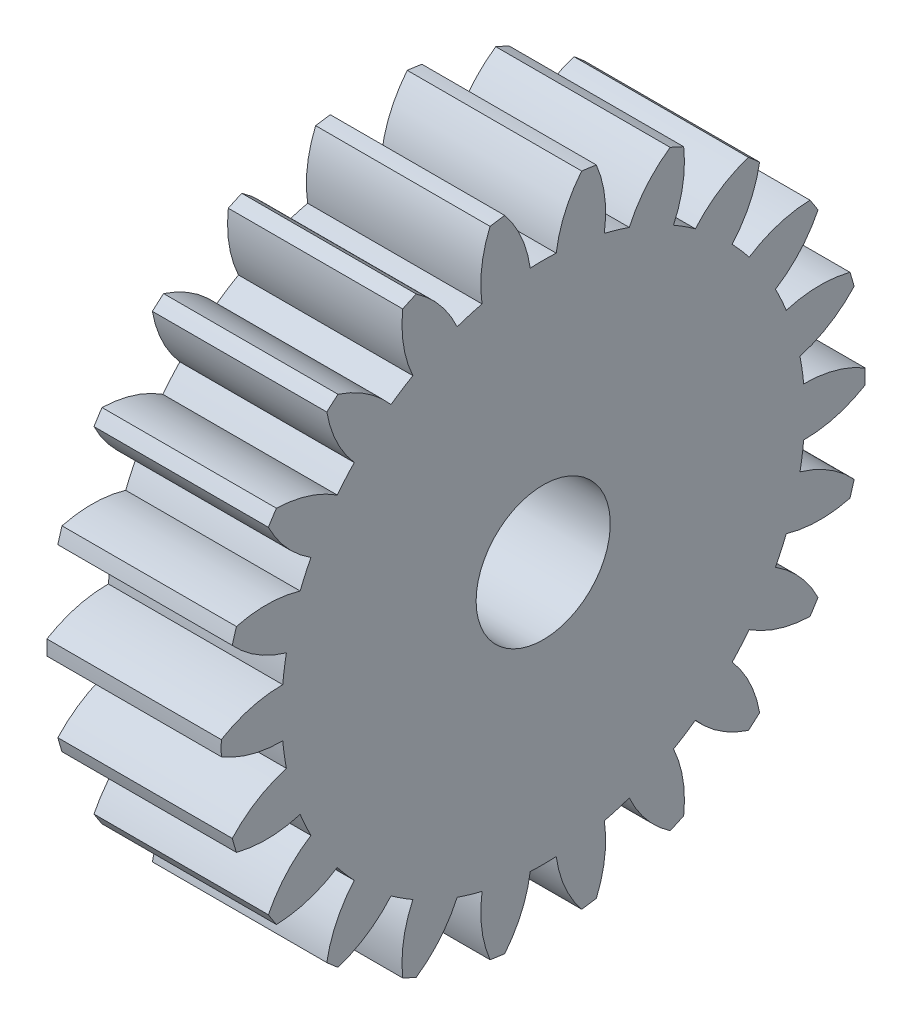
SolidWorks part; units mm, degrees
ref_plane "Plane1" through (0, 0, 0) normal (0, 0, 1) x (1, 0, 0)
ref_plane "Plane2" through (0, 0, 0) normal (0, 1, 0) x (1, 0, 0)
ref_plane "Plane3" through (0, 0, 0) normal (1, 0, 0) x (0, 0, -1)
other "Configuration Table"
sketch "HoldingSke" plane through (0, 0, 0) normal (0, 1, 0) x (1, 0, 0)
  line L0 (0, 0) -> (0.4636, -0.1873)
  line L1 (-15, 0) -> (100, 0) construction
  line L2 (0, 0) -> (-2.1039, 2.3779)
  line L3 (0, 0) -> (-11.863, 4.5341)
  line L4 (0, 0) -> (8.0072, 3.2351)
  line L5 (0, 0) -> (-15.9282, -5.9407)
  line L6 (0, 0) -> (-10.7765, -7.2709)
  line L7 (-2.1039, 2.3779) -> (1.5554, 18.9794)
  line L8 (-76.2, 54.61) -> (-74.4, 54.61)
  line L9 (-71.009, 38.7566) -> (-53.1078, 45.2721)
  line L10 (-76.2, 71.12) -> (104.1128, 71.12)
  line L11 (0, 0) -> (-13, 0)
  line L12 (-76.2, 101.6) -> (-76.133, 101.6)
  line L13 (24.9733, 27.94) -> (52.9518, 28.4284)
  line L14 (24.9733, 27.94) -> (24.9743, 27.94)
  line L15 (24.9733, 27.94) -> (100.4006, 29.5858)
  line L16 (-63.627, -2) -> (-12.827, -2)
  circle A0 centre (0, 0) radius 5
  circle A1 centre (0, 0) radius 6
  circle A2 centre (0, 0) radius 6
  circle A3 centre (0, 0) radius 5
  dimension "Num_teeth" = 22
  dimension "Pitch_radius" = 180.3128
  dimension "Width" = 13
  dimension "Thickness" = 13
sketch "BasProSke" plane through (0, 0, 0) normal (0, 1, 0) x (1, 0, 0)
  line L0 (-10, 0) -> (60, 0) construction
  line L1 (0, 0) -> (0, 24)
  line L2 (0, 0) -> (13, 0)
  line L3 (13, 0) -> (13, 24)
  line L4 (13, 24) -> (0, 24)
  dimension "Thickness" = 13
  dimension "Diameter" = 48
revolve "Base-Revolve" add sketch "BasProSke" angle 360 about L0
sketch "TooCutSke" plane through (0, 0, 0) normal (1, 0, 0) x (0, 0, -1)
  line L1 (0, 0) -> (0, 107) construction
  line L2 (0, 0) -> (-1.6867, 21.9352) construction
  line L3 (0, 0) -> (-6.2482, 43.4572) construction
  line L4 (-1.6867, 21.9352) -> (-3.1241, 21.7286) construction
  arc A0 (0.9682, 19.4749) -> (-0.9682, 19.4749) centre (0, 0) ccw
  arc A1 (2.8856, 23.8515) -> (-2.8856, 23.8515) centre (0, 0) ccw
  circle A2 centre (0, 0) radius 22 construction
  circle A3 centre (0, 0) radius 20.6732 construction
  arc A4 (-0.9682, 19.4749) -> (-2.8856, 23.8515) centre (-9.6845, 18.2645) ccw
  arc A5 (2.8856, 23.8515) -> (0.9682, 19.4749) centre (9.6845, 18.2645) ccw
extrude "ToothCut" cut sketch "TooCutSke" along normal through all
fillet "Breaks" [suppressed] radius 0.04 tangent propagation no
fillet "RootFillets" [suppressed] radius 0.501
pattern_circular "TeethCuts" count 22 every 16.364 about axis through (-10, 0, 0) along (1, 0, 0) of "ToothCut", "RootFillets", "Breaks"
sketch "HubNeaOneSke" plane through (0, 0, 0) normal (-1, 0, 0) x (0, 0, 1)
  circle A0 centre (0, 0) radius 6
  dimension "Diameter" = 12
extrude "HubNearOne" add sketch "HubNeaOneSke" along normal blind 4.0001
sketch "HubNeaBotSke" plane through (0, 0, 0) normal (-1, 0, 0) x (0, 0, 1)
  circle A0 centre (0, 0) radius 6
  dimension "Diameter" = 12
extrude "HubNearBoth" [suppressed] add sketch "HubNeaBotSke" along normal blind 2
ref_plane "FarPln" through (13, 0, 0) normal (1, 0, 0) x (0, 0, -1)
sketch "HubFarSke" plane through (13, 0, 0) normal (1, 0, 0) x (0, 0, -1)
  circle A0 centre (0, 0) radius 6
  dimension "Diameter" = 12
extrude "HubFar" [suppressed] add sketch "HubFarSke" along normal blind 2
sketch "BorSke" plane through (0, 0, 0) normal (1, 0, 0) x (0, 0, -1)
  circle A0 centre (0, 0) radius 5
  dimension "Diameter" = 10
extrude "Bore" cut sketch "BorSke" along normal mid plane 34.0001
sketch "KeySke" plane through (0, 0, 0) normal (1, 0, 0) x (0, 0, -1)
  line L0 (-2, 0) -> (-2, 6.8)
  line L1 (-2, 6.8) -> (2, 6.8)
  line L2 (2, 6.8) -> (2, 0)
  line L3 (0, 0) -> (0, 34) construction
  line L4 (-2, 0) -> (2, 0)
  dimension "Width" = 4
extrude "Keyway" [suppressed] cut sketch "KeySke" along normal mid plane 34.0001
pattern_circular "Keyway2" [suppressed] count 2 every 90 about axis through (-10, 0, 0) along (1, 0, 0) reverse direction yes
scale "Scale1" scale about centroid uniform scaling yes scale factor 0.317565
equation "' \"Module@HoldingSke\" = 6.35"
equation "' \"Num_teeth@HoldingSke\" = 12"
equation "' \"Ap@HoldingSke\" =  20"
equation "' \"Ap@HoldingSke\" = 20"
equation "' \"Width@HoldingSke\" = 0.5 * 25.4"
equation "' \"Hub_dia@HoldingSke\"= 1 * 25.4"
equation "' \"Hub_dia@HoldingSke\" = 1 * 25.4"
equation "' \"Overall_len@HoldingSke\" = 1.0 * 25.4"
equation "' \"Bore@HoldingSke\" = 0.75 * 25.4"
equation "' \"T_dim@HoldingSke\" = 0.1 * 25.4"
equation "' \"Width@KeySke\" = 0.25 * 25.4"
equation "' \"Show_teeth@HoldingSke\" = 13"
equation "' \"Backlash@HoldingSke\" = 0.009 * 25.4"
equation "' \"Addendum_fac@HoldingSke\" = 1.0"
equation "' \"Dedendum_fac@HoldingSke\" = 1.25"
equation "' \"Dedendum_add@HoldingSke\" = 0.00005 * 25.4"
equation "' \"Clearance_fac@HoldingSke\" = 0.25"
equation "\"Pitch@HoldingSke\" = 1 / \"Module@HoldingSke\""
equation "\"Overcut_dia@TooCutSke\" = (\"Num_teeth@HoldingSke\" + 2 * \"Addendum_fac@HoldingSke\") / \"Pitch@HoldingSke\" + 0.002 * 25.4"
equation "\"Pitch_dia@TooCutSke\" = \"Num_teeth@HoldingSke\" / \"Pitch@HoldingSke\""
equation "\"Base_dia@TooCutSke\" = \"Num_teeth@HoldingSke\" / \"Pitch@HoldingSke\" * cos((\"Ap@HoldingSke\"  * 3.14159265 / 180))"
equation "\"Root_dia@TooCutSke\" = (\"Num_teeth@HoldingSke\" + 2) / \"Pitch@HoldingSke\" - 2 * (\"Addendum_fac@HoldingSke\" + \"Dedendum_fac@HoldingSke\") / \"Pitch@HoldingSke\" - \"Dedendum_add@HoldingSke\" * 2"
equation "\"Half_ang@TooCutSke\" = 180 / \"Num_teeth@HoldingSke\""
equation "\"Half_CT@TooCutSke\" = \"Num_teeth@HoldingSke\" / \"Pitch@HoldingSke\" * sin((3.14159265 / 2 / \"Num_teeth@HoldingSke\")) / 2 - 7 * \"Backlash@HoldingSke\" / 4"
equation "\"Flank_rad@TooCutSke\" = \"Num_teeth@HoldingSke\" / \"Pitch@HoldingSke\" / 5"
equation "\"Radius@RootFillets\" = \"Clearance_fac@HoldingSke\" / \"Pitch@HoldingSke\" + \"Dedendum_add@HoldingSke\""
equation "\"Break_rad@Breaks\" = 0.02 / \"Pitch@HoldingSke\""
equation "\"Thickness@HoldingSke\" = \"Width@HoldingSke\""
equation "\"OAL@HoldingSke\" = \"Thickness@HoldingSke\""
equation "\"MHD@HoldingSke\" = (\"Num_teeth@HoldingSke\" + 2) / \"Pitch@HoldingSke\" - 2 * (\"Addendum_fac@HoldingSke\" + \"Dedendum_fac@HoldingSke\")  / \"Pitch@HoldingSke\" - \"Dedendum_add@HoldingSke\" * 2"
equation "\"MBD@HoldingSke\" = (\"Num_teeth@HoldingSke\" + 2) / \"Pitch@HoldingSke\" - 2 * (\"Addendum_fac@HoldingSke\" + \"Dedendum_fac@HoldingSke\")  / \"Pitch@HoldingSke\" - \"Dedendum_add@HoldingSke\" * 2 - 0.002 * 25.4"
equation "\"MHD@HoldingSke\" = ((sgn( \"MHD@HoldingSke\" - \"Hub_dia@HoldingSke\" )-1)*( \"MHD@HoldingSke\" - \"Hub_dia@HoldingSke\" ))/-2+ \"Hub_dia@HoldingSke\""
equation "\"MBD@HoldingSke\" = ((sgn( \"MBD@HoldingSke\" - \"Bore@HoldingSke\" )-1)*( \"MBD@HoldingSke\" - \"Bore@HoldingSke\" ))/-2+ \"Bore@HoldingSke\""
equation "\"OAL@HoldingSke\" = ((sgn( \"OAL@HoldingSke\" - \"Overall_len@HoldingSke\" )+1)*( \"OAL@HoldingSke\" - \"Overall_len@HoldingSke\" ))/2 + \"Overall_len@HoldingSke\" + 0.000002 * 25.4"
equation "\"Num_teeth@TeethCuts\" = int( \"Show_teeth@HoldingSke\" ) + 1"
equation "\"Num_teeth@TeethCuts\" = ((sgn( \"Num_teeth@TeethCuts\" - \"Num_teeth@HoldingSke\" )-1)*( \"Num_teeth@TeethCuts\" - \"Num_teeth@HoldingSke\" ))/-2+ \"Num_teeth@HoldingSke\""
equation "\"Num_teeth@TeethCuts\" = ((sgn( \"Num_teeth@TeethCuts\" - 2.0)+1)*( \"Num_teeth@TeethCuts\" - 2.0))/2 +2.0"
equation "\"Angle@TeethCuts\" = 360.0 / \"Num_teeth@HoldingSke\""
equation "\"Diameter@BasProSke\" = (\"Num_teeth@HoldingSke\" + 2 * \"Addendum_fac@HoldingSke\") / \"Pitch@HoldingSke\""
equation "\"Thickness@BasProSke\"  = \"Thickness@HoldingSke\""
equation "' \"Fillet_rad@BasProSke\" =  \"Thickness@HoldingSke\" * 0.05"
equation "' \"Fillet_rad@BasProSke\" = \"Thickness@HoldingSke\" * 0.05"
equation "\"MHD@HoldingSke\" = ((sgn( \"MHD@HoldingSke\" - \"Root_dia@TooCutSke\" )-1)*( \"MHD@HoldingSke\" - \"Root_dia@TooCutSke\" ))/-2+ \"Root_dia@TooCutSke\""
equation "\"Diameter@HubNeaOneSke\" = \"MHD@HoldingSke\""
equation "\"Length@HubNearOne\" = \"OAL@HoldingSke\" - \"Thickness@BasProSke\""
equation "\"Diameter@HubNeaBotSke\" = \"MHD@HoldingSke\""
equation "\"Length@HubNearBoth\" = ( \"OAL@HoldingSke\" - \"Thickness@BasProSke\" ) / 2.0"
equation "\"Thickness@FarPln\" = \"Thickness@BasProSke\""
equation "\"Diameter@HubFarSke\" = \"MHD@HoldingSke\""
equation "\"Length@HubFar\" = ( \"OAL@HoldingSke\" - \"Thickness@BasProSke\" ) / 2.0"
equation "\"Diameter@BorSke\" = \"MBD@HoldingSke\""
equation "\"D1@Bore\" = \"OAL@HoldingSke\" * 2.0"
equation "\"D1@Keyway\" = \"OAL@HoldingSke\" * 2.0"
equation "\"Offset@KeySke\" = \"T_dim@HoldingSke\" + \"MBD@HoldingSke\" / 2.0"
